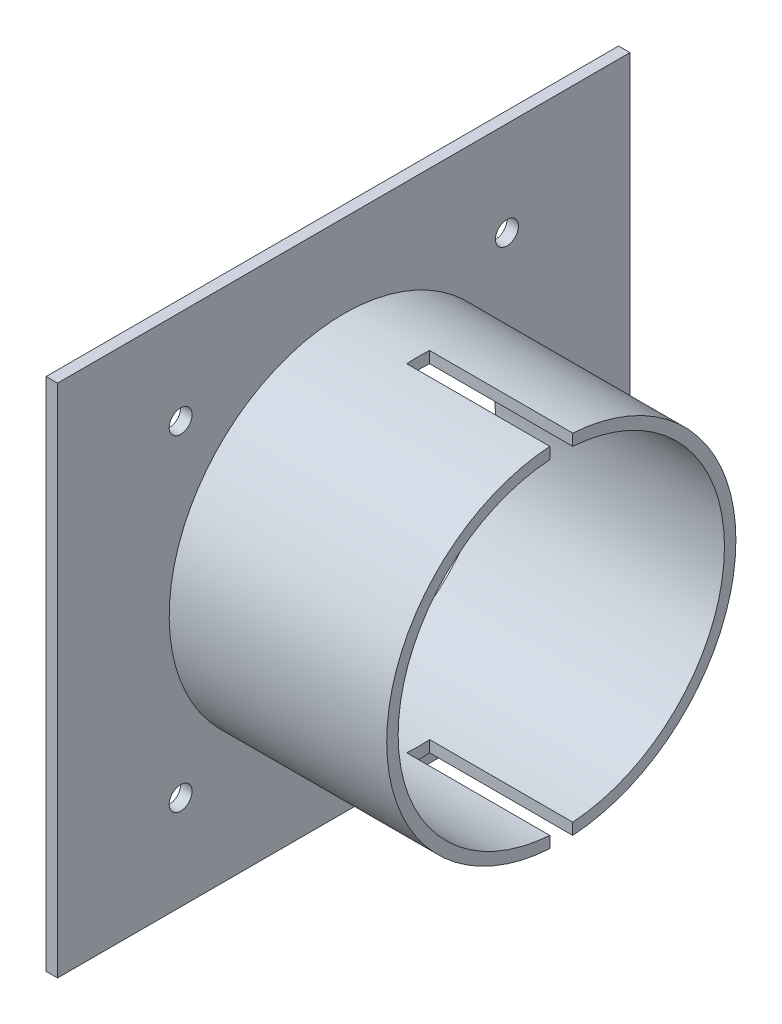
SolidWorks part; units mm, degrees
material "PVC Rígido"
ref_plane "Alzado" through (0, 0, 0) normal (0, 0, 1) x (1, 0, 0)
ref_plane "Planta" through (0, 0, 0) normal (0, 1, 0) x (1, 0, 0)
ref_plane "Vista lateral" through (0, 0, 0) normal (1, 0, 0) x (0, 0, -1)
sketch "Croquis1" plane through (0, 0, 0) normal (1, 0, 0) x (0, 0, -1)
  line L0 (0, 90) -> (0, -90) construction
  line L1 (-100, 90) -> (100, 90)
  line L2 (-100, 90) -> (-100, -90)
  line L3 (-100, -90) -> (100, -90)
  line L4 (100, 90) -> (100, -90)
  line L5 (-100, 90) -> (100, -90) construction
  line L6 (-100, -90) -> (100, 90) construction
  line L7 (57, -57) -> (-57, -57) construction
  line L8 (57, -57) -> (57, 57) construction
  line L9 (57, 57) -> (-57, 57) construction
  line L10 (-57, -57) -> (-57, 57) construction
  line L11 (57, -57) -> (-57, 57) construction
  line L12 (57, 57) -> (-57, -57) construction
  line L13 (-100, 0) -> (100, 0) construction
  circle A0 centre (0, 0) radius 57
  circle A1 centre (-57, 57) radius 4
  circle A2 centre (57, 57) radius 4
  circle A3 centre (57, -57) radius 4
  circle A4 centre (-57, -57) radius 4
  point P0 (0, 0)
  dimension "D2" = 180
  dimension "D1" = 200
extrude "Saliente-Extruir1" add sketch "Croquis1" along normal blind 4
sketch "Croquis2" plane through (4, 0, 0) normal (1, 0, 0) x (0, 0, -1)
  circle A0 centre (0, 0) radius 57
  circle A1 centre (0, 0) radius 61
  dimension "D1" = 4
extrude "Saliente-Extruir2" add sketch "Croquis2" along normal blind 76
sketch "Croquis3" plane through (80, 0, 0) normal (1, 0, 0) x (0, 0, -1)
  line L0 (-57, 0) -> (57, 0) construction
  line L1 (4, -68.5818) -> (-4, -45.4182) construction
  line L2 (4, 45.4182) -> (-4, 45.4182)
  line L3 (4, 45.4182) -> (4, 68.5818)
  line L4 (4, 68.5818) -> (-4, 68.5818)
  line L5 (-4, 45.4182) -> (-4, 68.5818)
  line L6 (4, 45.4182) -> (-4, 68.5818) construction
  line L7 (4, 68.5818) -> (-4, 45.4182) construction
  line L8 (4, -45.4182) -> (-4, -68.5818) construction
  line L9 (-4, -45.4182) -> (-4, -68.5818)
  line L10 (4, -68.5818) -> (-4, -68.5818)
  line L11 (4, -45.4182) -> (-4, -45.4182)
  line L12 (4, -45.4182) -> (4, -68.5818)
  circle A0 centre (0, 0) radius 57 construction
  point P5 (0, 57)
  point P14 (0, -57)
  dimension "D1" = 8
extrude "Cortar-Extruir1" cut sketch "Croquis3" against normal blind 50
